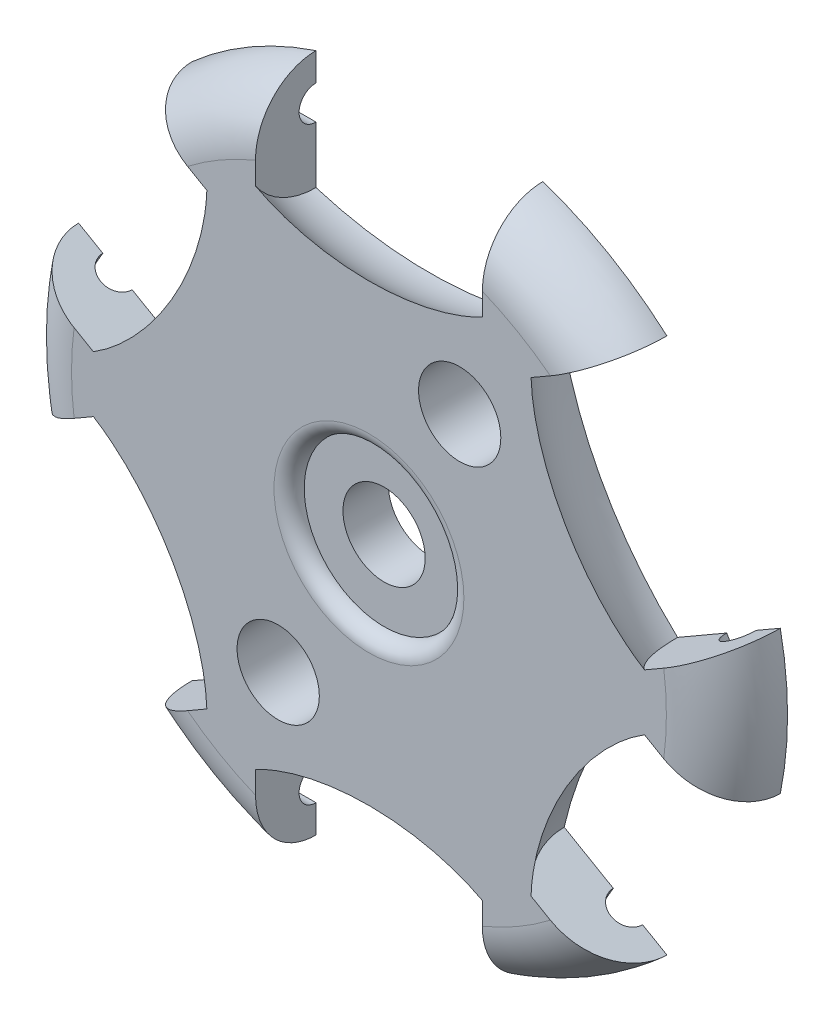
SolidWorks part; units mm, degrees
ref_plane "Front Plane" through (0, 0, 0) normal (0, 0, 1) x (1, 0, 0)
ref_plane "Top Plane" through (0, 0, 0) normal (0, 1, 0) x (1, 0, 0)
ref_plane "Right Plane" through (0, 0, 0) normal (1, 0, 0) x (0, 0, -1)
sketch "Sketch1" plane through (0, 0, 0) normal (0, 0, 1) x (1, 0, 0)
  circle A0 centre (0, 0) radius 18.796
  dimension "D1" = 37.592
extrude "Boss-Extrude1" add sketch "Sketch1" along normal blind 3.175
fillet "Fillet1" radius 3.1852 1 edges at (18.796, 0, 3.175)
sketch "Sketch2" plane through (0, 0, 3.175) normal (0, 0, 1) x (1, 0, 0)
  line L0 (-4.7625, -8.2489) -> (4.7625, 8.2489) construction
  line L1 (0, 0) -> (0, 6.4682) construction
  circle A0 centre (4.7625, 8.2489) radius 2.159
  circle A1 centre (-4.7625, -8.2489) radius 2.159
  circle A4 centre (0, 0) radius 2.159
  point P9 (0, 0)
  dimension "D2" = 4.318
  dimension "D4" = 4.318
  dimension "D1" = 9.525
  dimension "D5" = 30
  dimension "D3" = 2
extrude "Cut-Extrude1" cut sketch "Sketch2" against normal through all
sketch "Sketch5" plane through (0, 0, 0) normal (0, 0, 1) x (1, 0, 0)
  line L0 (-5.9531, 15.4686) -> (5.9531, 15.4686)
  line L1 (5.9531, 15.4686) -> (5.9531, 19.3354)
  line L2 (-5.9531, 15.4686) -> (-5.9531, 19.3354)
  line L3 (-5.9531, 15.4686) -> (-8.5086, 15.4686) construction
  arc A0 (-5.9531, 19.3354) -> (5.9531, 19.3354) centre (0, 0) cw
  circle A1 centre (0, 0) radius 18.796 construction
  point P5 (0, 15.4686)
  point P9 (0, 20.2311)
  dimension "D1" = 11.9062
  dimension "D2" = 15.4686
  dimension "D3" = 9.525
revolve "Cut-Revolve1" cut sketch "Sketch5" angle 360 about L3
sketch "Sketch6" plane through (0, 0, 0) normal (1, 0, 0) x (0, 0, -1)
  line L0 (0, -18.796) -> (0, 17.8283) construction
  circle A0 centre (0, 15.4686) radius 0.889
  arc A1 (-3.175, 13.2614) -> (0, 11.6018) centre (0, 15.4686) ccw construction
  dimension "D1" = 1.778
extrude "Cut-Extrude2" cut sketch "Sketch6" against normal mid plane 15.875
pattern_circular "CirPattern1" count 6 over 360 about axis through (0, 0, 0) along (0, 0, 1) of "Cut-Revolve1", "Cut-Extrude2"
sketch "Sketch8" plane through (0, 0, 3.175) normal (0, 0, 1) x (1, 0, 0)
  line L1 (0, 5.1326) -> (-4.445, 2.5663)
  line L2 (-4.445, 2.5663) -> (-4.445, -2.5663)
  line L3 (-4.445, -2.5663) -> (0, -5.1326)
  line L4 (0, -5.1326) -> (4.445, -2.5663)
  line L5 (4.445, -2.5663) -> (4.445, 2.5663)
  line L6 (4.445, 2.5663) -> (0, 5.1326)
  circle A0 centre (0, 0) radius 4.445 construction
  dimension "D1" = 8.89
extrude "Cut-Extrude4" [suppressed] cut sketch "Sketch8" against normal blind 1.5875
sketch "Sketch9" plane through (0, 0, 3.175) normal (0, 0, 1) x (1, 0, 0)
  circle A0 centre (0, 0) radius 4.191
  dimension "D1" = 8.382
extrude "Cut-Extrude5" cut sketch "Sketch9" against normal blind 0.7937
fillet "Fillet2" radius 0.7937 1 edges at (4.191, 0, 3.175)
